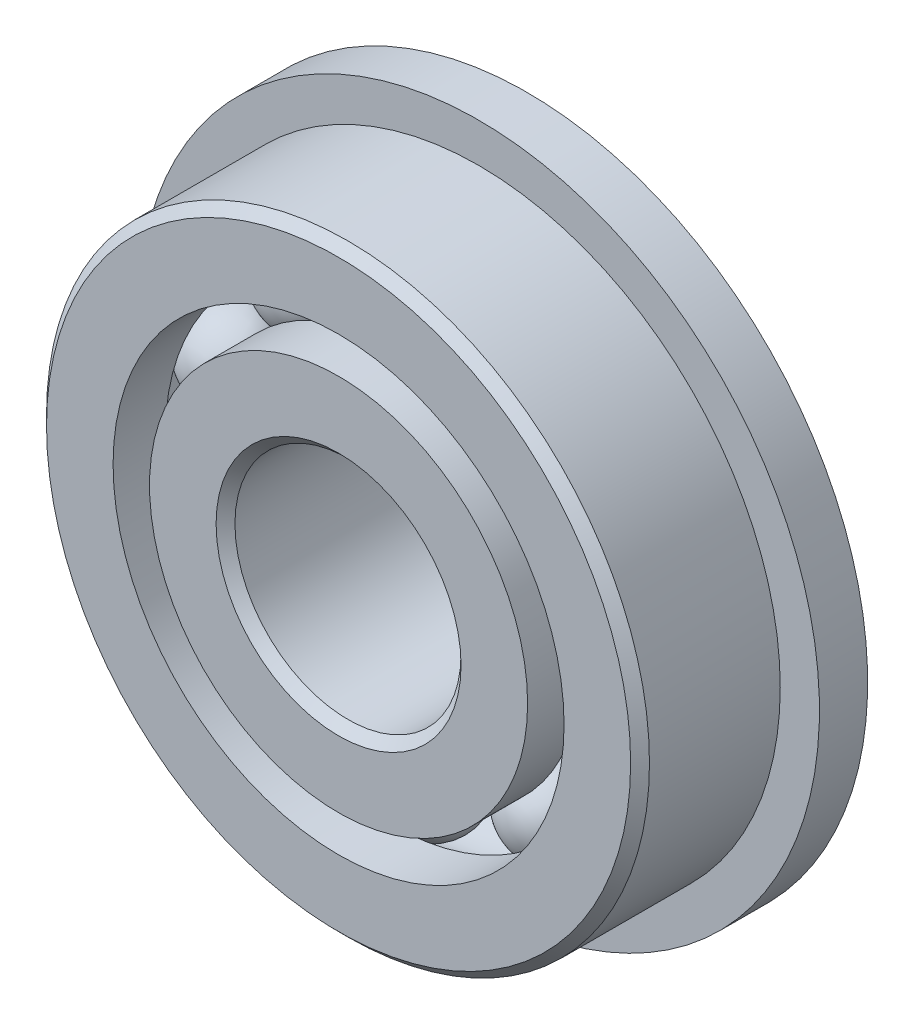
SolidWorks part; units mm, degrees
ref_plane "Front Plane" through (0, 0, 0) normal (0, 0, 1) x (1, 0, 0)
ref_plane "Top Plane" through (0, 0, 0) normal (0, 1, 0) x (1, 0, 0)
ref_plane "Right Plane" through (0, 0, 0) normal (1, 0, 0) x (0, 0, -1)
sketch "Sketch1" plane through (0, 0, 0) normal (1, 0, 0) x (0, 0, -1)
  line L0 (-1.9844, 0) -> (1.9844, 0) construction
  line L1 (0, 6.35) -> (0, -6.35) construction
  line L2 (1.7859, 6.35) -> (-1.7859, 6.35)
  line L3 (-1.7859, 6.35) -> (-1.9844, 6.1516)
  line L4 (-1.9844, 6.1516) -> (-1.9844, 4.7494)
  line L5 (-1.9844, 4.7494) -> (-0.8819, 4.7494)
  line L6 (1.9844, 4.7494) -> (0.8819, 4.7494)
  line L7 (1.9844, 6.1516) -> (1.9844, 4.7494)
  line L8 (1.7859, 6.35) -> (1.9844, 6.1516)
  line L9 (0, 6.35) -> (0, 4.3656) construction
  line L10 (0, 4.3656) -> (0, 2.3813) construction
  arc A0 (-0.8819, 4.7494) -> (0.8819, 4.7494) centre (0, 4.3656) cw
  point P14 (0, 2.3813)
  dimension "Width" = 3.9688
  dimension "OD" = 12.7
  dimension "D1" = 45
  dimension "D2" = 0.1984
  dimension "Shaft Dia" = 4.7625
  dimension "D3" = 1.7639
  dimension "D4" = 0.3838
revolve "Revolve1" add sketch "Sketch1" angle 360 about L0
sketch "Sketch3" plane through (0, 0, 0) normal (1, 0, 0) x (0, 0, -1)
  line L0 (-1.9844, 3.9818) -> (-0.8819, 3.9818)
  line L1 (0, 6.35) -> (0, -6.35) construction
  line L2 (-1.9844, 6.1516) -> (-1.9844, 4.7494) construction
  line L3 (-1.9844, 3.9818) -> (-1.9844, 2.5797)
  line L4 (-1.7859, 6.35) -> (-1.9844, 6.1516) construction
  line L5 (-1.9844, 2.5797) -> (-1.7859, 2.3813)
  line L6 (-1.7859, 2.3813) -> (1.7859, 2.3813)
  line L7 (1.7859, 6.35) -> (1.7859, -6.35) construction
  line L8 (1.7859, 2.3813) -> (1.9844, 2.5797)
  line L9 (1.9844, -6.1516) -> (1.9844, 6.1516) construction
  line L10 (1.9844, 2.5797) -> (1.9844, 3.9818)
  line L11 (1.9844, 3.9818) -> (0.8819, 3.9818)
  line L13 (1.7859, 6.35) -> (1.9844, 6.1516) construction
  arc A0 (0.8819, 4.7494) -> (-0.8819, 4.7494) centre (0, 4.3656) ccw construction
  arc A1 (0.8819, 3.9818) -> (-0.8819, 3.9818) centre (0, 4.3656) cw
revolve "Revolve3" add sketch "Sketch3" angle 360 about L0
sketch "Sketch4" plane through (0, 0, 0) normal (1, 0, 0) x (0, 0, -1)
  line L0 (-0.9618, 4.3656) -> (0.9618, 4.3656)
  arc A2 (-0.9618, 4.3656) -> (0.9618, 4.3656) centre (0, 4.3656) cw
  arc A3 (0.8819, 4.7494) -> (-0.8819, 4.7494) centre (0, 4.3656) ccw construction
revolve "Revolve4" add sketch "Sketch4" angle 360 about L0
ref_axis "Axis1" through (0, 0, -1.9844) along (0, 0, 1)
pattern_circular "CirPattern1" count 10 every 36 about axis through (0, 0, -1.9844) along (0, 0, 1) of bodies 104
sketch "Sketch5" plane through (0, 0, 0) normal (1, 0, 0) x (0, 0, -1)
  line L0 (-1.9844, 4.7494) -> (-0.8819, 4.7494) construction
  line L1 (-1.8852, 4.7494) -> (-0.9618, 4.7494)
  line L2 (-1.8852, 4.7494) -> (-1.8852, 3.9818)
  line L3 (-1.8852, 3.9818) -> (-0.9618, 3.9818)
  line L4 (-0.9618, 4.7494) -> (-0.9618, 3.9818)
  line L5 (-1.9844, 3.9818) -> (-0.8819, 3.9818) construction
  line L6 (1.9844, 4.7494) -> (0.8819, 4.7494) construction
  line L7 (1.8852, 4.7494) -> (0.9618, 4.7494)
  line L8 (1.8852, 4.7494) -> (1.8852, 3.9818)
  line L9 (1.8852, 3.9818) -> (0.9618, 3.9818)
  line L10 (0.9618, 4.7494) -> (0.9618, 3.9818)
  line L11 (1.9844, 3.9818) -> (0.8819, 3.9818) construction
  line L12 (-1.7859, 6.35) -> (-1.9844, 6.1516) construction
  point P18 (-1.8852, 6.2508)
revolve "Revolve5" [suppressed] add sketch "Sketch5" angle 360 about L0
sketch "Sketch6" plane through (0, 0, 0) normal (1, 0, 0) x (0, 0, -1)
  line L0 (1.9844, 0) -> (-1.9844, 0) construction
  line L1 (1.9844, 4.7494) -> (0.9684, 4.7494)
  line L2 (1.9844, 4.7494) -> (1.9844, 7.1755)
  line L3 (1.9844, 7.1755) -> (0.9684, 7.1755)
  line L4 (0.9684, 4.7494) -> (0.9684, 7.1755)
  dimension "Th" = 1.016
  dimension "Flange OD" = 14.351
revolve "Revolve6" add sketch "Sketch6" angle 360 about L0
equation "\"D2@Sketch1\" = \"Width@Sketch1\"*.05"
equation "\"D3@Sketch1\" = \"Width@Sketch1\"/2.25"
equation "\"D4@Sketch1\" = (((\"OD@Sketch1\"-\"Width@Sketch1\")/2)/3.25)/3.5"
equation "\"D2@CirPattern1\" = 360/\"Balls@CirPattern1\""
